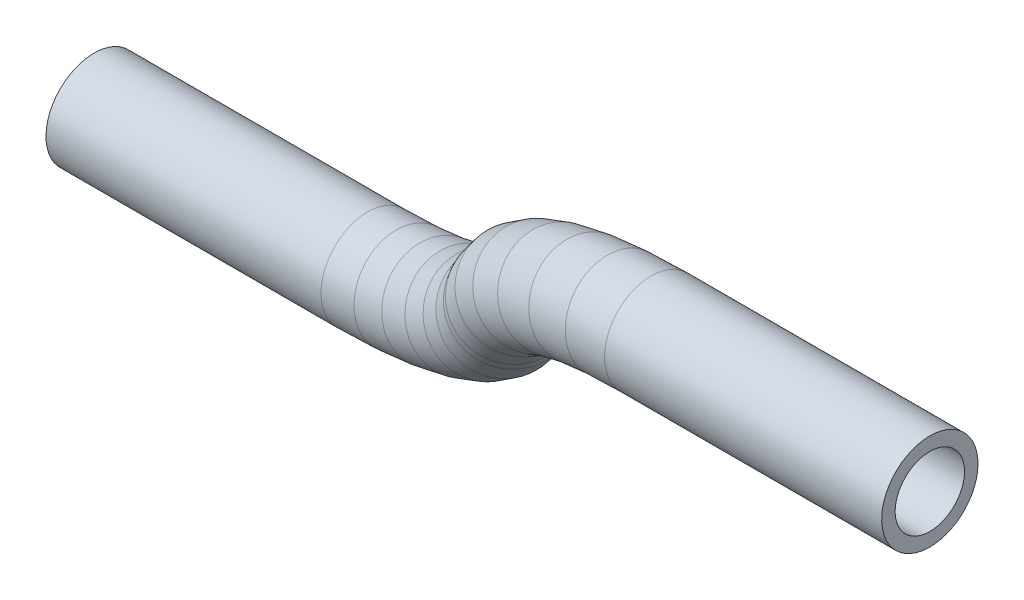
SolidWorks part; units mm, degrees
ref_plane "Front Plane" through (0, 0, 0) normal (0, 0, 1) x (1, 0, 0)
ref_plane "Top Plane" through (0, 0, 0) normal (0, 1, 0) x (1, 0, 0)
ref_plane "Right Plane" through (0, 0, 0) normal (1, 0, 0) x (0, 0, -1)
sketch3d "Path"
  line L0 (-31.3, -15.2562, -16.9437) -> (-49.5, -15.2562, -16.9437)
  line L1 (-49.5, -15.2562, -16.9437) -> (-51.9822, -15.4371, -17.0439)
  line L2 (-51.9822, -15.4371, -17.0439) -> (-54.3959, -15.9749, -17.3416)
  line L3 (-54.3959, -15.9749, -17.3416) -> (-56.6747, -16.8546, -17.8288)
  line L4 (-56.6747, -16.8546, -17.8288) -> (-58.7556, -18.0522, -18.4919)
  line L5 (-58.7556, -18.0522, -18.4919) -> (-60.5813, -19.5345, -19.3126)
  line L6 (-60.5813, -19.5345, -19.3126) -> (-62.1014, -21.2606, -20.2684)
  line L7 (-62.1014, -21.2606, -20.2684) -> (-62.6439, -21.9956, -20.6753)
  line L8 (-62.6439, -21.9956, -20.6753) -> (-64.164, -23.7217, -21.6311)
  line L9 (-64.164, -23.7217, -21.6311) -> (-65.9897, -25.204, -22.4518)
  line L10 (-65.9897, -25.204, -22.4518) -> (-68.0707, -26.4015, -23.1149)
  line L11 (-68.0707, -26.4015, -23.1149) -> (-70.3494, -27.2813, -23.6021)
  line L12 (-70.3494, -27.2813, -23.6021) -> (-72.7631, -27.8191, -23.8998)
  line L13 (-72.7631, -27.8191, -23.8998) -> (-75.2453, -28, -24)
  line L14 (-75.2453, -28, -24) -> (-93.4453, -28, -24)
ref_plane "Start Plane" through (-31.3, 0, 0) normal (1, 0, 0) x (0, 0, -1)
sketch "Profile" plane through (-31.3, 0, 0) normal (1, 0, 0) x (0, 0, -1)
  circle A0 centre (16.9437, -15.2562) radius 3.175
  circle A1 centre (16.9437, -15.2562) radius 2.286
sweep "Tube" add profiles "Profile" path "Path"
ref_axis "Engine Axis" through (-28.1927, 0, 0) along (-1, 0, 0)
